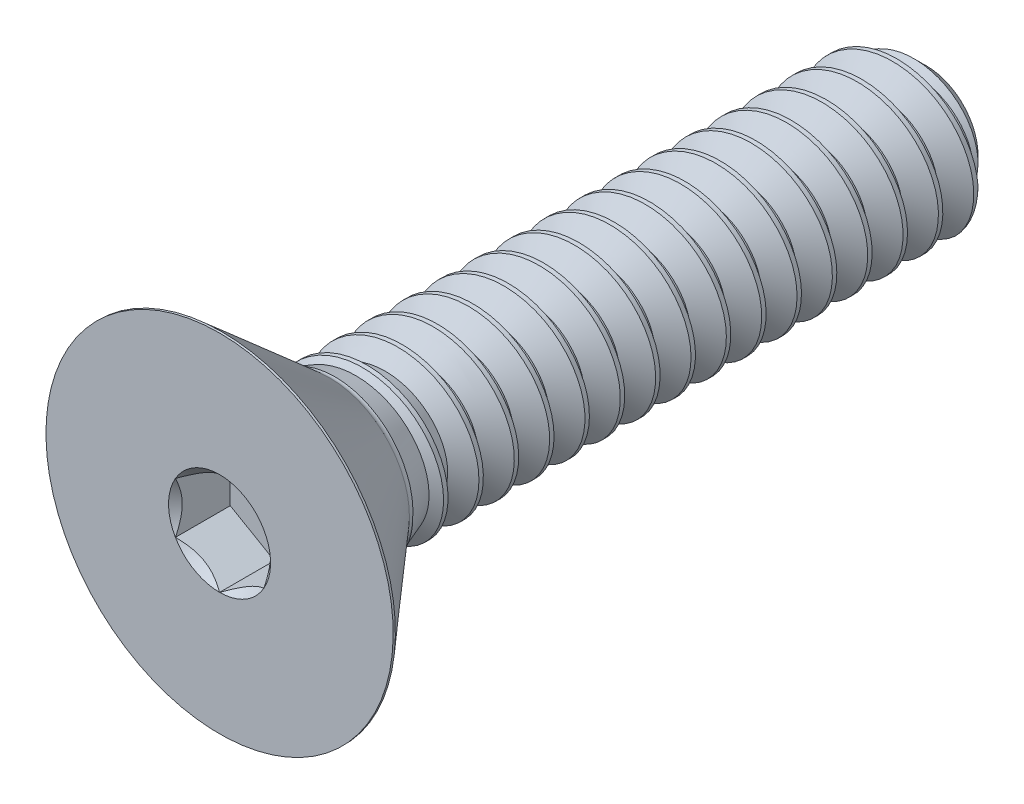
SolidWorks part; units mm, degrees
ref_plane "Front Plane" through (0, 0, 0) normal (0, 0, 1) x (1, 0, 0)
ref_plane "Top Plane" through (0, 0, 0) normal (0, 1, 0) x (1, 0, 0)
ref_plane "Right Plane" through (0, 0, 0) normal (1, 0, 0) x (0, 0, -1)
sketch "Sketch1" plane through (0, 0, 0) normal (1, 0, 0) x (0, 0, -1)
  line L0 (-7.9375, 0) -> (7.9375, 0) construction
  line L1 (-7.9375, 0) -> (-7.9375, 3.8989)
  line L2 (-7.9375, 3.8989) -> (-7.8882, 3.8989)
  line L3 (-7.8882, 3.8989) -> (-5.4737, 1.8)
  line L4 (-7.8882, -3.8989) -> (-5.4737, -1.8)
  line L5 (7.9375, 0) -> (7.9375, 1.7526)
  line L6 (7.9375, 1.7526) -> (-5.4737, 1.7526)
  line L7 (7.3422, 1.7526) -> (7.9375, 1.1573)
  line L8 (7.8879, 1.8385) -> (8.2848, 1.1511) construction
  line L9 (8.2848, 1.1511) -> (8.6816, 1.8385) construction
  line L10 (8.6816, 1.8385) -> (7.8879, 1.8385) construction
  line L11 (7.9127, 1.7956) -> (8.6568, 1.7956)
  line L12 (8.6568, 1.7956) -> (8.3344, 1.237)
  line L13 (8.3344, 1.237) -> (8.2352, 1.237)
  line L14 (8.2352, 1.237) -> (7.9127, 1.7956)
  line L15 (8.2848, 1.237) -> (8.2848, 1.1511) construction
  line L16 (7.9375, 1.7526) -> (8.632, 1.7526) construction
  line L17 (8.2848, 1.8385) -> (8.2848, 1.7526) construction
  line L18 (7.9375, -1.7526) -> (-5.4737, -1.7526)
  arc A0 (-5.4737, 1.8) -> (-5.347, 1.7526) centre (-5.347, 1.9458) ccw
  point P2 (0, 0)
  point P23 (-6.7056, 0)
  point P27 (8.2848, 1.7956)
  point P30 (6.7469, -1.7526)
  point P31 (-5.4737, 3.8989)
  point P34 (-7.8882, -3.8989)
  dimension "Length" = 15.875
  dimension "Head Height" = 2.4638
  dimension "Head Diameter" = 7.7978
  dimension "Countersink Angle" = 82
  dimension "Screw Size Decimal Equivalent" = 3.5052
  dimension "Pitch" = 0.7937
  dimension "D4" = 0.0992
  dimension "D3" = 45
  dimension "D5" = 0.5953
  dimension "D6" = 1.2319
  dimension "D1" = 1.1906
  dimension "D7" = 0.0493
sketch "Sketch8" plane through (0, 0, 0) normal (0, 0, 1) x (1, 0, 0)
  line L1 (0, 1.1457) -> (-0.9922, 0.5728)
  line L2 (-0.9922, 0.5728) -> (-0.9922, -0.5728)
  line L3 (-0.9922, -0.5728) -> (0, -1.1457)
  line L4 (0, -1.1457) -> (0.9922, -0.5728)
  line L5 (0.9922, -0.5728) -> (0.9922, 0.5728)
  line L6 (0.9922, 0.5728) -> (0, 1.1457)
  circle A0 centre (0, 0) radius 0.9922 construction
  dimension "Drive Size" = 1.9844
sketch "Sketch2" plane through (0, 0, 0) normal (1, 0, 0) x (0, 0, -1)
  line L0 (-7.8882, 3.8989) -> (-5.4737, 1.8) construction
  line L1 (-7.9375, 0) -> (-7.9375, 3.8989) construction
  line L2 (-7.8882, 3.8989) -> (-5.4737, 1.8)
  line L3 (-7.9375, 0) -> (-7.9375, 3.8989)
  line L4 (-7.9375, 3.8989) -> (-7.8882, 3.8989) construction
  line L5 (-7.9375, 3.8989) -> (-7.8882, 3.8989)
  line L6 (-5.347, 1.7526) -> (7.3422, 1.7526)
  line L7 (7.3422, 1.7526) -> (7.9375, 1.1573)
  line L8 (7.9375, 1.1573) -> (7.9375, 0)
  line L9 (7.9375, 0) -> (-7.9375, 0)
  arc A0 (-5.4737, 1.8) -> (-5.347, 1.7526) centre (-5.347, 1.9458) ccw construction
  arc A1 (-5.4737, 1.8) -> (-5.347, 1.7526) centre (-5.347, 1.9458) ccw
revolve "Revolve1" add sketch "Sketch2" angle 360 about L9
sketch "Sketch9" plane through (0, 0, 7.9375) normal (0, 0, 1) x (1, 0, 0)
  line L0 (0.9922, -0.5728) -> (0.9922, 0.5728) construction
  line L1 (0, -1.1457) -> (0.9922, -0.5728) construction
  line L2 (-0.9922, -0.5728) -> (0, -1.1457) construction
  line L3 (-0.9922, 0.5728) -> (-0.9922, -0.5728) construction
  line L4 (0, 1.1457) -> (-0.9922, 0.5728) construction
  line L5 (0.9922, 0.5728) -> (0, 1.1457) construction
  line L6 (0.9922, -0.5728) -> (0.9922, 0.5728)
  line L7 (0, -1.1457) -> (0.9922, -0.5728)
  line L8 (-0.9922, -0.5728) -> (0, -1.1457)
  line L9 (-0.9922, 0.5728) -> (-0.9922, -0.5728)
  line L10 (0, 1.1457) -> (-0.9922, 0.5728)
  line L11 (0.9922, 0.5728) -> (0, 1.1457)
sketch "Sketch10" plane through (0, 0, 7.9375) normal (0, 0, 1) x (1, 0, 0)
  circle A0 centre (0, 0) radius 1.1457
extrude "Cut-Extrude2" cut sketch "Sketch10" against normal up to vertex (1.2319 mm away) draft 45 up to point (0, 0, 6.7056)
extrude "Cut-Extrude1" cut sketch "Sketch9" against normal up to vertex (1.2319 mm away) up to point (0, 0, 6.7056)
ref_plane "Plane1" through (0, 0, 5.347) normal (0, 0, 1) x (1, 0, 0)
split "Split1" trim tools "Plane1" bodies to split 111 resulting bodies 105 106
sketch "Sketch3" plane through (0, 0, -7.9375) normal (0, 0, -1) x (-1, 0, 0)
  circle A0 centre (0, 0) radius 1.7526 construction
  circle A1 centre (0, 0) radius 1.7526
curve "Helix/Spiral1" pitch 0.7937 height 15.875 radius 1.7526 centre (0, 0, -7.9375) axis (0, 0, 1) start towards (0, 1, 0)
sketch "Sketch4" plane through (0, 0, 0) normal (1, 0, 0) x (0, 0, -1)
  line L0 (7.9127, 1.7956) -> (8.6568, 1.7956) construction
  line L1 (8.2352, 1.237) -> (7.9127, 1.7956) construction
  line L2 (8.3344, 1.237) -> (8.2352, 1.237) construction
  line L3 (8.6568, 1.7956) -> (8.3344, 1.237) construction
  line L4 (7.9127, 1.7956) -> (8.6568, 1.7956)
  line L5 (8.2352, 1.237) -> (7.9127, 1.7956)
  line L6 (8.3344, 1.237) -> (8.2352, 1.237)
  line L7 (8.6568, 1.7956) -> (8.3344, 1.237)
sweep "Cut-Sweep1" cut profiles "Sketch4" path "Helix/Spiral1" align with end faces yes
sketch "Sketch7" plane through (0, 0, 5.347) normal (0, 0, 1) x (1, 0, 0)
  circle A0 centre (0, 0) radius 1.7526
extrude "Boss-Extrude2" add sketch "Sketch7" against normal up to next (13.2845 mm away) draft 20
equation "\"D4@Sketch1\" = \"Pitch@Sketch1\" / 8"
equation "\"D5@Sketch1\"=\"Pitch@Sketch1\"*0.75"
equation "\"D4@Helix/Spiral1\"=\"Pitch@Sketch1\""
equation "\"D3@Helix/Spiral1\"=\"Length@Sketch1\""
equation "\"D6@Sketch1\"=\"Head Height@Sketch1\"/2"
equation "\"D1@Sketch1\"=\"Pitch@Sketch1\"*1.5"
equation "\"D7@Sketch1\"=\"Head Height@Sketch1\"*0.02"
